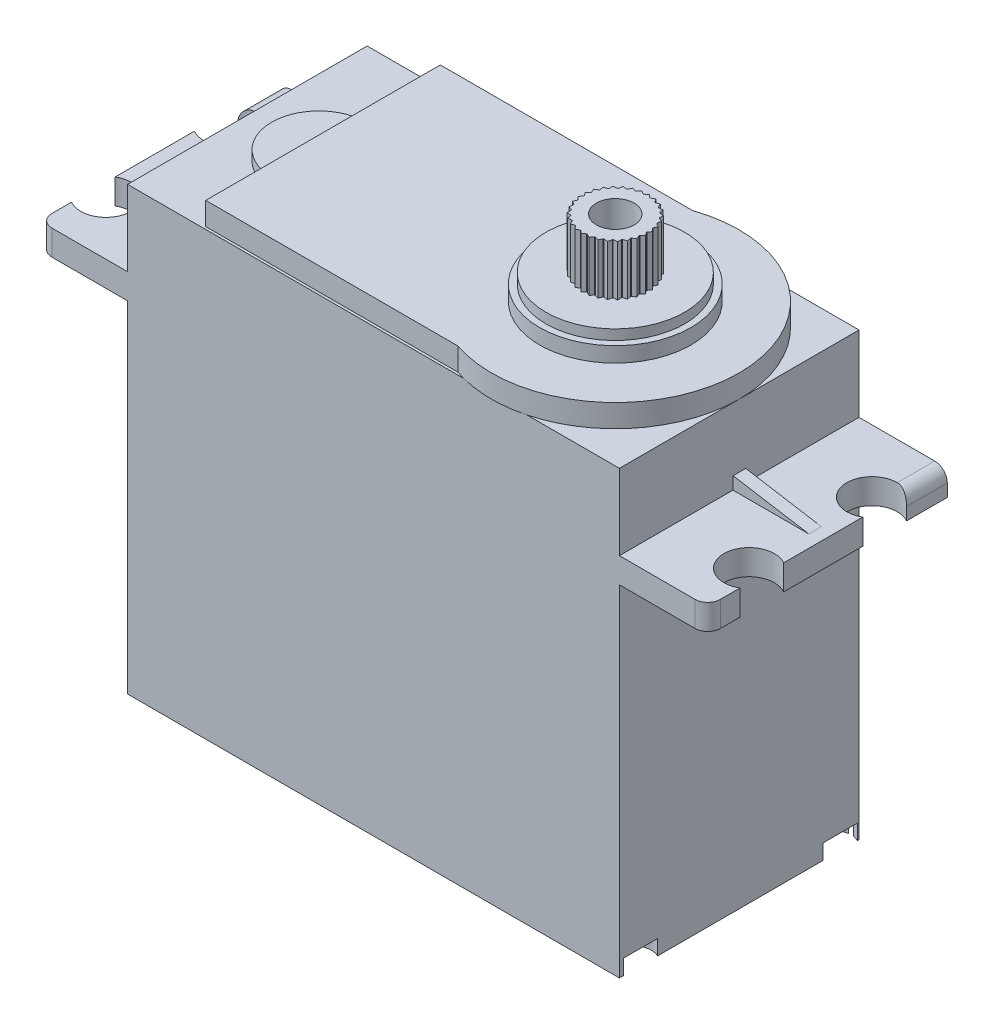
SolidWorks part; units mm, degrees
ref_plane "Front Plane" through (0, 0, 0) normal (0, 0, 1) x (1, 0, 0)
ref_plane "Top Plane" through (0, 0, 0) normal (0, 1, 0) x (1, 0, 0)
ref_plane "Right Plane" through (0, 0, 0) normal (1, 0, 0) x (0, 0, -1)
sketch "Sketch1" plane through (0, 0, 0) normal (0, 0, 1) x (1, 0, 0)
  line L1 (-23.6834, 8.2704) -> (15.3166, 8.2704)
  line L2 (-23.6834, 8.2704) -> (-23.6834, -26.7296)
  line L3 (-23.6834, -26.7296) -> (15.3166, -26.7296)
  line L4 (15.3166, 8.2704) -> (15.3166, -26.7296)
  dimension "D1" = 39
  dimension "D2" = 35
extrude "Boss-Extrude1" add sketch "Sketch1" along normal blind 19
sketch "Sketch2" plane through (0, 0, 19) normal (0, 0, 1) x (1, 0, 0)
  line L0 (15.3166, 8.2704) -> (15.3166, 2.2704) construction
  line L1 (15.3166, -26.7296) -> (15.3166, 8.2704) construction
  line L2 (-4.1834, 8.2704) -> (-4.1834, -3.6681) construction
  line L3 (15.3166, 2.2704) -> (22.3166, 2.2704)
  line L4 (15.3166, 2.2704) -> (15.3166, 0.2704)
  line L5 (15.3166, 0.2704) -> (22.3166, 0.2704)
  line L6 (22.3166, 2.2704) -> (22.3166, 0.2704)
  line L7 (15.3166, 8.2704) -> (-23.6834, 8.2704) construction
  line L8 (-30.6834, 2.2704) -> (-30.6834, 0.2704)
  line L9 (-23.6834, 2.2704) -> (-23.6834, 0.2704)
  line L10 (-23.6834, 0.2704) -> (-30.6834, 0.2704)
  line L11 (-23.6834, 2.2704) -> (-30.6834, 2.2704)
  dimension "D1" = 6
  dimension "D2" = 2
  dimension "D3" = 7
extrude "Boss-Extrude2" add sketch "Sketch2" against normal blind 19
ref_plane "Plane1" through (0, 0, 9.5) normal (0, 0, 1) x (1, 0, 0)
sketch "Sketch3" plane through (0, 0, 9.5) normal (0, 0, 1) x (1, 0, 0)
  line L0 (15.3336, 3.2723) -> (15.3336, 2.2723)
  line L1 (15.3336, 2.2723) -> (21.3336, 2.2723)
  line L2 (21.3336, 2.2723) -> (15.3336, 3.2723)
  line L3 (-23.6233, 8.3074) -> (15.2904, 8.3074) construction
  line L4 (-4.1665, 8.3074) -> (-4.1665, 2.2723) construction
  line L5 (-29.6665, 2.2723) -> (-23.6665, 3.2723)
  line L6 (-23.6665, 2.2723) -> (-29.6665, 2.2723)
  line L7 (-23.6665, 3.2723) -> (-23.6665, 2.2723)
  dimension "D1" = 1
  dimension "D2" = 6
extrude "Boss-Extrude3" add sketch "Sketch3" along normal mid plane 1
sketch "Sketch4" plane through (0, 2.2704, 0) normal (0, 1, 0) x (1, 0, 0)
  line L0 (21.3166, -14.7107) -> (21.3166, -19.7107) construction
  line L1 (21.3166, -4.967) -> (21.3166, 0) construction
  line L2 (22.3166, 0) -> (15.3166, 0) construction
  line L3 (15.3166, -14.7107) -> (21.3166, -14.7107) construction
  line L4 (15.3166, -19) -> (15.3166, 0) construction
  line L5 (15.3166, -4.967) -> (21.3166, -4.967) construction
  line L6 (-4.1834, 0) -> (-4.1834, -4.967) construction
  line L7 (15.3166, 0) -> (-23.6834, 0) construction
  circle A0 centre (21.3166, -14.7107) radius 2
  circle A1 centre (21.3166, -4.967) radius 2
  circle A2 centre (-29.6834, -14.7107) radius 2
  circle A3 centre (-29.6834, -4.967) radius 2
  dimension "D2" = 4
  dimension "D3" = 4
  dimension "D4" = 6
  dimension "D1" = 5
extrude "Cut-Extrude1" cut sketch "Sketch4" against normal blind 3
fillet "Fillet1" radius 1 4 edges at (-30.6834, 1.2704, 19) (-30.6834, 2.2704, 1.6175) (22.3166, 2.2704, 1.6175) (22.3166, 1.2704, 19)
sketch "Sketch5" plane through (0, 8.2704, 0) normal (0, 1, 0) x (1, 0, 0)
  line L0 (15.3166, -19) -> (-23.6834, -19) construction
  line L4 (-17.6834, -0.2) -> (-17.6834, -18.8)
  line L5 (-17.6834, -18.8) -> (2.3166, -18.8)
  line L6 (2.3166, -0.2) -> (-17.6834, -0.2)
  line L7 (-23.6834, -19) -> (-23.6834, 0) construction
  line L8 (15.3166, 0) -> (-23.6834, 0) construction
  arc A1 (2.3166, -0.2) -> (2.3166, -18.8) centre (5.49, -9.5) cw
  dimension "D1" = 0.2
  dimension "D2" = 0.2
  dimension "D3" = 6
  dimension "D4" = 20
extrude "Boss-Extrude4" add sketch "Sketch5" along normal blind 1.8
sketch "Sketch6" plane through (0, -26.7296, 0) normal (0, -1, 0) x (1, 0, 0)
  circle A0 centre (-22.6606, 17.3297) radius 1.5
  circle A1 centre (-22.6606, 1.4871) radius 1.5
  circle A2 centre (14.6705, 17.3297) radius 1.5
  circle A3 centre (14.6705, 1.4871) radius 1.5
  dimension "D1" = 3
extrude "Cut-Extrude2" cut sketch "Sketch6" against normal blind 1.2
sketch "Sketch7" plane through (0, 10.0704, 0) normal (0, 1, 0) x (1, 0, 0)
  line L0 (15.3166, -9.5) -> (5.49, -9.5) construction
  arc A0 (2.3166, -18.8) -> (2.3166, -0.2) centre (5.49, -9.5) ccw construction
  circle A1 centre (5.49, -9.5) radius 6
  dimension "D1" = 12
extrude "Boss-Extrude5" add sketch "Sketch7" along normal blind 1.2
sketch "Sketch8" plane through (0, 11.2704, 0) normal (0, 1, 0) x (1, 0, 0)
  circle A0 centre (5.49, -9.5) radius 5.5
  dimension "D1" = 11
extrude "Boss-Extrude6" add sketch "Sketch8" along normal blind 0.8
sketch "Sketch9" plane through (0, 8.2704, 0) normal (0, 1, 0) x (1, 0, 0)
  line L0 (-17.6834, -0.2) -> (-17.6834, -18.8) construction
  line L1 (-17.6834, -6.0659) -> (-17.6834, -13.5751)
  arc A0 (-17.6834, -6.0659) -> (-17.6834, -13.5751) centre (-17.6834, -9.8205) ccw
extrude "Boss-Extrude7" add sketch "Sketch9" along normal blind 0.8
sketch "Sketch10" plane through (0, 12.0704, 0) normal (0, 1, 0) x (1, 0, 0)
  circle A0 centre (5.49, -9.5) radius 2.5
  dimension "D1" = 5
extrude "Boss-Extrude8" add sketch "Sketch10" along normal blind 4
sketch "Sketch11" plane through (0, 16.0704, 0) normal (0, 1, 0) x (1, 0, 0)
  line L0 (5.5034, -6.8019) -> (5.2631, -7.0103)
  line L1 (5.2631, -7.0103) -> (5.7367, -7.0122)
  line L2 (5.7367, -7.0122) -> (5.5034, -6.8019)
  circle A0 centre (5.49, -9.5) radius 2.5 construction
extrude "Boss-Extrude9" add sketch "Sketch11" against normal blind 4
pattern_circular "CirPattern2" count 30 over 360 about axis through (5.49, 16.0704, 9.5) along (0, 1, 0) of "Boss-Extrude9"
sketch "Sketch12" plane through (0, 16.0704, 0) normal (0, 1, 0) x (1, 0, 0)
  circle A0 centre (5.49, -9.5) radius 1.5
  dimension "D1" = 3
extrude "Cut-Extrude4" cut sketch "Sketch12" against normal blind 4
sketch "Sketch13" plane through (0, 16.0704, 0) normal (0, 1, 0) x (1, 0, 0)
  circle A0 centre (5.49, -9.5) radius 2.8
  dimension "D1" = 5.6
